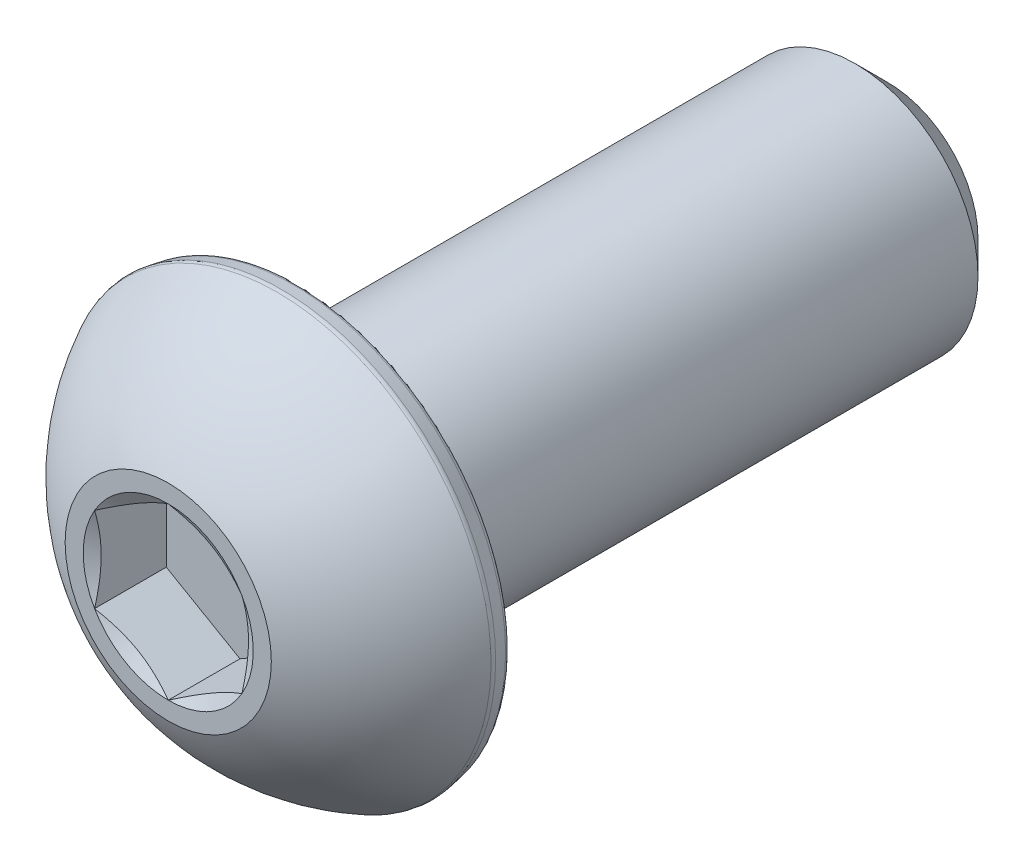
SolidWorks part; units mm, degrees
ref_plane "Front Plane" through (0, 0, 0) normal (0, 0, 1) x (1, 0, 0)
ref_plane "Top Plane" through (0, 0, 0) normal (0, 1, 0) x (1, 0, 0)
ref_plane "Right Plane" through (0, 0, 0) normal (1, 0, 0) x (0, 0, -1)
sketch "Sketch1" plane through (0, 0, 0) normal (1, 0, 0) x (0, 0, -1)
  line L0 (-11.6332, 0) -> (11.6332, 0) construction
  line L1 (-11.6332, 0) -> (-11.6332, 6.9469)
  line L2 (-11.6332, 6.9469) -> (-7.4168, 6.9469)
  line L3 (-7.4168, 6.9469) -> (-7.4168, 3.9751)
  line L4 (-7.4168, 3.9751) -> (11.6332, 3.9751)
  line L5 (11.6332, 3.9751) -> (11.6332, 0)
  point P2 (0, 0)
  point P4 (10.2221, 0)
  point P9 (9.5165, 3.9751)
  point P10 (9.5165, -3.9751)
  point P11 (11.6332, -3.9751)
  point P15 (-9.3142, 0)
  dimension "Head Height" = 4.2164
  dimension "Head Diameter" = 13.8938
  dimension "Length" = 19.05
  dimension "Screw Size Decimal Equivalent" = 7.9502
  dimension "Thread Pitch" = 1.4111
  dimension "D1" = 2.1167
  dimension "D2" = 2.319
sketch "Sketch2" plane through (0, 0, 0) normal (0, 0, 1) x (1, 0, 0)
  line L0 (0, 3.9751) -> (0, 0) construction
  line L1 (0, 2.7496) -> (-2.3813, 1.3748)
  line L2 (-2.3813, 1.3748) -> (-2.3812, -1.3748)
  line L3 (-2.3812, -1.3748) -> (0, -2.7496)
  line L4 (0, -2.7496) -> (2.3813, -1.3748)
  line L5 (2.3813, -1.3748) -> (2.3813, 1.3748)
  line L6 (2.3813, 1.3748) -> (0, 2.7496)
  circle A0 centre (0, 0) radius 2.3813 construction
  circle A1 centre (0, 0) radius 3.3337
  point P10 (0, 3.3337)
  dimension "D1" = 6.6675
  dimension "Drive Size" = 4.7625
sketch "Sketch3" plane through (0, 0, 0) normal (1, 0, 0) x (0, 0, -1)
  line L0 (-11.6332, 0) -> (-11.6332, 3.3337)
  line L1 (-11.6332, 0) -> (-11.6332, 6.9469) construction
  line L2 (-11.6332, 6.9469) -> (-7.4168, 6.9469) construction
  line L3 (-8.0493, 6.9469) -> (-7.4168, 6.8354)
  line L4 (-7.4168, 6.9469) -> (-7.4168, 3.9751) construction
  line L5 (-7.4168, 6.8354) -> (-7.4168, 3.9751)
  line L6 (-11.6332, 0) -> (11.6332, 0) construction
  line L7 (-11.6332, 0) -> (11.6332, 0)
  line L8 (11.6332, 0) -> (11.6332, 2.9168)
  line L9 (11.6332, 3.9751) -> (11.6332, 0) construction
  line L10 (11.6332, 2.9168) -> (10.5749, 3.9751)
  line L11 (-7.4168, 3.9751) -> (11.6332, 3.9751) construction
  line L12 (10.5749, 3.9751) -> (-7.4168, 3.9751)
  arc A0 (-11.6332, 3.3337) -> (-8.0493, 6.9469) centre (-4.659, 0) cw
  dimension "D1" = 0.6325
  dimension "D2" = 10
  dimension "D3" = 45
  dimension "D4" = 1.0583
revolve "Revolve1" add sketch "Sketch3" angle 360 about L7
sketch "Sketch4" plane through (0, 0, 11.6332) normal (0, 0, 1) x (1, 0, 0)
  line L0 (-2.3812, -1.3748) -> (0, -2.7496) construction
  line L1 (-2.3813, 1.3748) -> (-2.3812, -1.3748) construction
  line L2 (0, 2.7496) -> (-2.3813, 1.3748) construction
  line L3 (2.3813, 1.3748) -> (0, 2.7496) construction
  line L4 (2.3813, -1.3748) -> (2.3813, 1.3748) construction
  line L5 (0, -2.7496) -> (2.3813, -1.3748) construction
  line L6 (-2.3812, -1.3748) -> (0, -2.7496)
  line L7 (-2.3813, 1.3748) -> (-2.3812, -1.3748)
  line L8 (0, 2.7496) -> (-2.3813, 1.3748)
  line L9 (2.3813, 1.3748) -> (0, 2.7496)
  line L10 (2.3813, -1.3748) -> (2.3813, 1.3748)
  line L11 (0, -2.7496) -> (2.3813, -1.3748)
extrude "Cut-Extrude1" cut sketch "Sketch4" against normal up to vertex (2.319 mm away) up to point (0, 0, 9.3142)
sketch "Sketch5" plane through (0, 0, 11.6332) normal (0, 0, 1) x (1, 0, 0)
  circle A0 centre (0, 0) radius 2.7496
extrude "Cut-Extrude2" cut sketch "Sketch5" against normal up to vertex (2.319 mm away) draft 60 up to point (0, 0, 9.3142)
fillet "Fillet1" radius 0.2108 2 edges at (6.9469, 0, 8.0493) (6.8354, 0, 7.4168)
split "Split1" [suppressed] bodies to split 106
sketch "Sketch6" [suppressed] plane through (0, 0, -11.6332) normal (0, 0, -1) x (-1, 0, 0)
  circle A0 centre (0, 0) radius 3.9751 construction
  circle A1 centre (0, 0) radius 3.9751
curve "Helix/Spiral1" [suppressed] pitch 1.4111 height 20.4611 turns 14.5
sketch "Sketch7" [suppressed] plane through (0, 0, 0) normal (1, 0, 0) x (0, 0, -1)
  line L0 (11.545, 4.1279) -> (12.2506, 2.9058) construction
  line L1 (12.2506, 2.9058) -> (12.9561, 4.1279) construction
  line L2 (12.9561, 4.1279) -> (11.545, 4.1279) construction
  line L3 (11.5891, 4.0515) -> (12.912, 4.0515)
  line L4 (12.912, 4.0515) -> (12.3388, 3.0586)
  line L5 (12.3388, 3.0586) -> (12.1624, 3.0586)
  line L6 (12.1624, 3.0586) -> (11.5891, 4.0515)
  line L7 (12.2506, 3.0586) -> (12.2506, 2.9058) construction
  line L8 (11.6332, 3.9751) -> (12.8679, 3.9751) construction
  line L9 (12.2506, 4.1279) -> (12.2506, 3.9751) construction
  point P12 (12.2506, 4.0515)
  dimension "D1" = 1.4111
  dimension "D2" = 0.1764
sweep "Cut-Sweep1" [suppressed] cut profiles "Sketch7" path "Helix/Spiral1"
sketch "Sketch8" [suppressed] plane through (0, 0, 7.4168) normal (0, 0, -1) x (-1, 0, 0)
  circle A0 centre (0, 0) radius 4.1279
extrude "Boss-Extrude1" [suppressed] add sketch "Sketch8" along normal up to vertex draft 45 up to point (0, 3.9751, -9.5165)
equation "\"D1@Sketch1\"=\"Thread Pitch@Sketch1\"*1.5"
equation "\"D2@Sketch1\"=0.55*\"Head Height@Sketch1\""
equation "\"D1@Sketch2\"=\"Drive Size@Sketch2\"*1.4"
equation "\"D1@Sketch3\"=0.15*\"Head Height@Sketch1\""
equation "\"D4@Sketch3\"=0.75*\"Thread Pitch@Sketch1\""
equation "\"D1@Fillet1\"=.05*\"Head Height@Sketch1\""
equation "\"D4@Helix/Spiral1\"=\"Thread Pitch@Sketch1\""
equation "\"D3@Helix/Spiral1\"=\"Length@Sketch1\"+\"Thread Pitch@Sketch1\""
equation "\"D2@Sketch7\"=\"D1@Sketch7\"/8"
equation "\"D1@Sketch7\"=\"Thread Pitch@Sketch1\""
